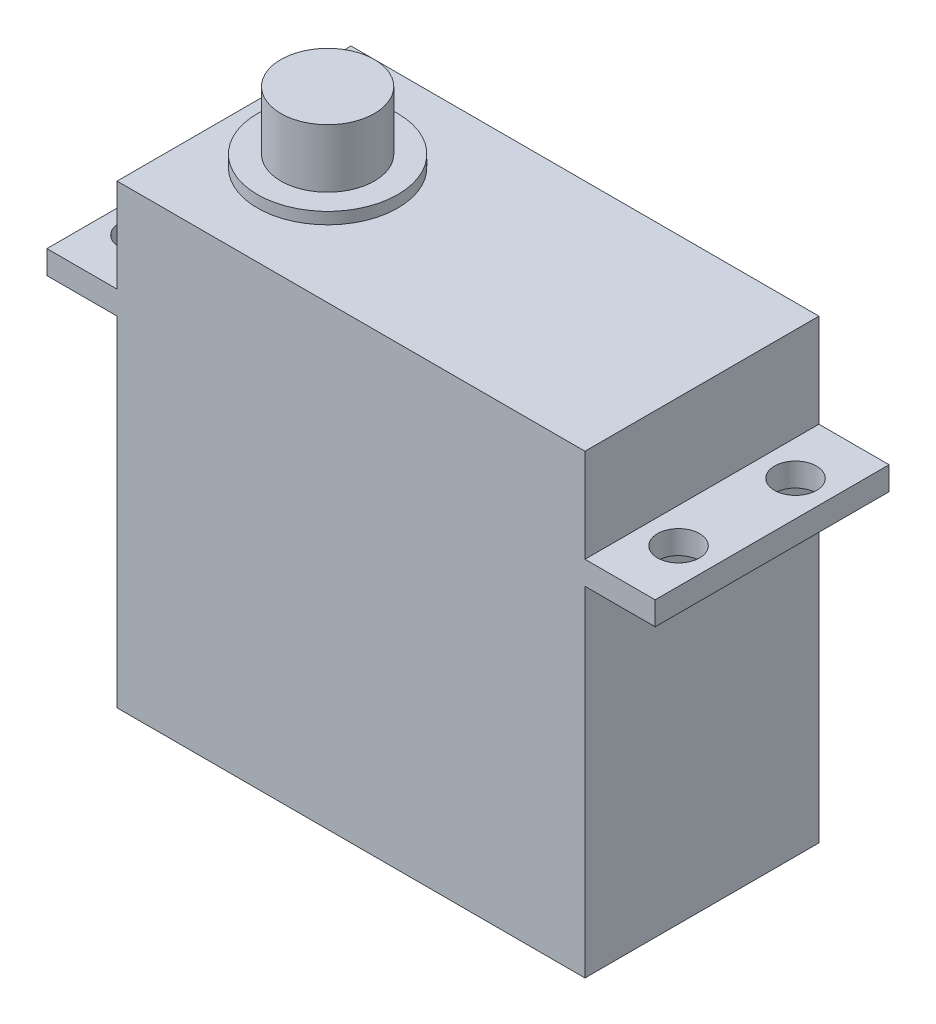
SolidWorks part; units mm, degrees
ref_plane "前视基准面" through (0, 0, 0) normal (0, 0, 1) x (1, 0, 0)
ref_plane "上视基准面" through (0, 0, 0) normal (0, 1, 0) x (1, 0, 0)
ref_plane "右视基准面" through (0, 0, 0) normal (1, 0, 0) x (0, 0, -1)
other "Configuration Table"
sketch "草图1" plane through (0, 0, 0) normal (0, 0, 1) x (1, 0, 0)
  line L1 (0, 0) -> (40, 0)
  line L2 (0, 0) -> (0, 39)
  line L3 (0, 39) -> (40, 39)
  line L4 (40, 0) -> (40, 39)
  point P6 (0, 0)
extrude "凸台-拉伸1" add sketch "草图1" along normal blind 20
sketch "草图2" plane through (0, 39, 0) normal (0, 1, 0) x (1, 0, 0)
  circle A0 centre (8, -10) radius 6
extrude "凸台-拉伸2" add sketch "草图2" along normal blind 1
sketch "草图3" plane through (0, 40, 0) normal (0, 1, 0) x (1, 0, 0)
  circle A0 centre (8, -10) radius 4
extrude "凸台-拉伸3" add sketch "草图3" along normal blind 5
sketch "草图4" plane through (0, 0, 0) normal (-1, 0, 0) x (0, 0, 1)
  line L11 (0, 39) -> (0, 0) construction
  line L16 (0, 31) -> (20, 31)
  line L17 (0, 31) -> (0, 29)
  line L18 (0, 29) -> (20, 29)
  line L19 (20, 31) -> (20, 29)
  line L20 (20, 39) -> (20, 0) construction
extrude "凸台-拉伸4" add sketch "草图4" along normal blind 6
sketch "草图5" plane through (0, 31, 0) normal (0, 1, 0) x (1, 0, 0)
  circle A0 centre (-3, -5) radius 1.8
  circle A1 centre (-3, -15) radius 1.8
  point P4 (0, 0)
  point P5 (0, 0)
extrude "切除-拉伸1" cut sketch "草图5" against normal blind 6
ref_plane "基准面1" through (-6, 31, 0) normal (1, 0, 0) x (0, 0, -1)
sketch "草图8" plane through (40, 0, 0) normal (1, 0, 0) x (0, 0, -1)
  line L0 (-20, 0) -> (-20, 39) construction
  line L1 (-20, 31) -> (0, 31)
  line L2 (-20, 31) -> (-20, 29)
  line L3 (-20, 29) -> (0, 29)
  line L4 (0, 31) -> (0, 29)
  line L5 (0, 0) -> (0, 39) construction
extrude "凸台-拉伸5" add sketch "草图8" along normal blind 6
sketch "草图9" plane through (0, 31, 0) normal (0, 1, 0) x (1, 0, 0)
  circle A0 centre (43, -5) radius 1.8
  circle A1 centre (43, -15) radius 1.8
  point P4 (0, 0)
extrude "切除-拉伸2" cut sketch "草图9" against normal blind 6
